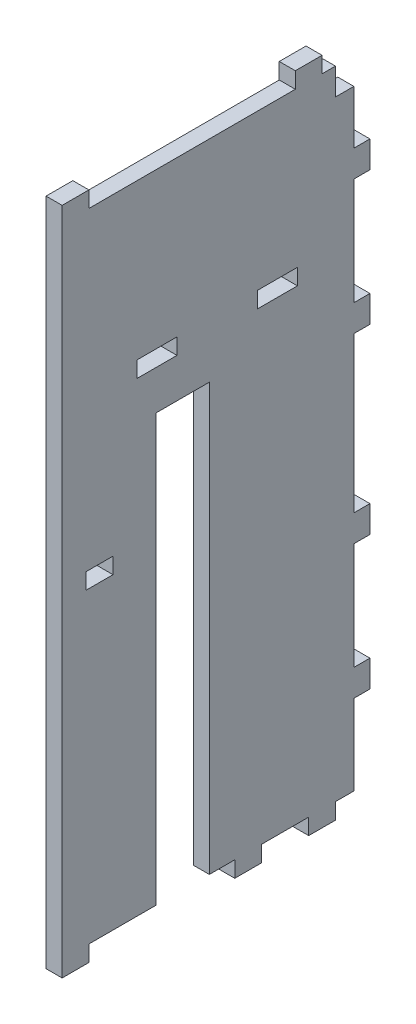
SolidWorks part; units mm, degrees
ref_plane "Plan de face" through (0, 0, 0) normal (0, 0, 1) x (1, 0, 0)
ref_plane "Plan de dessus" through (0, 0, 0) normal (0, 1, 0) x (1, 0, 0)
ref_plane "Plan de droite" through (0, 0, 0) normal (1, 0, 0) x (0, 0, -1)
sketch "Esquisse1" plane through (0, 0, 0) normal (1, 0, 0) x (0, 0, -1)
  line L0 (97.1531, 0) -> (-102.2664, 0) construction
  line L1 (-54.5, 119) -> (54.5, 119)
  line L2 (-54.5, 119) -> (-54.5, -119)
  line L3 (-54.5, -119) -> (54.5, -119)
  line L4 (54.5, 119) -> (54.5, -119)
  line L5 (0, 172.7153) -> (0, -236.1933) construction
  line L7 (-45.5, 2) -> (-35.5, 2)
  line L8 (-45.5, 2) -> (-45.5, -4)
  line L9 (-45.5, -4) -> (-35.5, -4)
  line L10 (-35.5, 2) -> (-35.5, -4)
  line L15 (-26.585, 61) -> (-11.585, 61)
  line L16 (-26.585, 61) -> (-26.585, 55)
  line L17 (-26.585, 55) -> (-11.585, 55)
  line L18 (-11.585, 61) -> (-11.585, 55)
  line L19 (18.415, 61) -> (33.415, 61)
  line L20 (18.415, 61) -> (18.415, 55)
  line L21 (18.415, 55) -> (33.415, 55)
  line L22 (33.415, 61) -> (33.415, 55)
  dimension "D1" = 238
  dimension "D2" = 109
  dimension "D4" = 119
  dimension "D13" = 15
  dimension "D14" = 15
  dimension "D15" = 30
  dimension "D16" = 6
  dimension "D17" = 6
  dimension "D3" = 54.5
  dimension "D5" = 58
  dimension "D6" = 27.915
  dimension "D7" = 9
  dimension "D8" = 117
  dimension "D9" = 6
  dimension "D10" = 10
extrude "Boss.-Extru.1" add sketch "Esquisse1" along normal blind 6
sketch "Esquisse3" plane through (6, 0, 0) normal (1, 0, 0) x (0, 0, -1)
  line L0 (-54.5, -119) -> (54.5, -119) construction
  line L1 (-54.5, -119) -> (-44.5, -119)
  line L2 (-54.5, -119) -> (-54.5, -125)
  line L3 (-54.5, -125) -> (-44.5, -125)
  line L4 (-44.5, -119) -> (-44.5, -125)
  line L5 (245.3741, 0) -> (-166.5298, 0) construction
  line L6 (54.5, -119) -> (54.5, 119) construction
  line L7 (37.62, -119) -> (47.62, -119)
  line L8 (37.62, -119) -> (37.62, -125)
  line L9 (37.62, -125) -> (47.62, -125)
  line L10 (0, 208.6671) -> (0, -232.3841) construction
  line L11 (-54.5, -119) -> (54.5, -119) construction
  line L12 (47.62, -119) -> (47.62, -125)
  line L13 (60.5, 39) -> (60.5, 29)
  line L14 (54.5, 29) -> (60.5, 29)
  line L15 (54.5, 39) -> (54.5, 29)
  line L16 (54.5, 39) -> (60.5, 39)
  line L17 (60.5, 89) -> (60.5, 79)
  line L18 (54.5, 79) -> (60.5, 79)
  line L19 (54.5, 89) -> (54.5, 79)
  line L20 (54.5, 89) -> (60.5, 89)
  line L21 (54.5, 119) -> (-54.5, 119) construction
  line L22 (54.5, -89) -> (60.5, -89)
  line L23 (54.5, -89) -> (54.5, -79)
  line L24 (54.5, -79) -> (60.5, -79)
  line L25 (60.5, -89) -> (60.5, -79)
  line L26 (54.5, -39) -> (60.5, -39)
  line L27 (54.5, -39) -> (54.5, -29)
  line L28 (54.5, -29) -> (60.5, -29)
  line L29 (0, -208.6671) -> (0, 232.3841) construction
  line L30 (10, -119) -> (20, -119)
  line L31 (10, -119) -> (10, -125)
  line L32 (10, -125) -> (20, -125)
  line L33 (20, -119) -> (20, -125)
  line L34 (54.5, -119) -> (54.5, 119) construction
  line L35 (60.5, -39) -> (60.5, -29)
  line L36 (42.62, 119) -> (32.62, 119)
  line L37 (42.62, 119) -> (42.62, 125)
  line L38 (42.62, 125) -> (32.62, 125)
  line L39 (32.62, 119) -> (32.62, 125)
  line L50 (-44.5, 119) -> (-44.5, 125)
  line L51 (-54.5, 125) -> (-44.5, 125)
  line L52 (-54.5, 119) -> (-54.5, 125)
  line L53 (-54.5, 119) -> (-44.5, 119)
  dimension "D2" = 10
  dimension "D3" = 6
  dimension "D4" = 10
  dimension "D5" = 6.88
  dimension "D6" = 6
  dimension "D7" = 6
  dimension "D8" = 10
  dimension "D9" = 6
  dimension "D10" = 10
  dimension "D11" = 6
  dimension "D12" = 10
  dimension "D13" = 17.62
  dimension "D14" = 30
  dimension "D15" = 40
  dimension "D16" = 6
  dimension "D17" = 10
  dimension "D18" = 11.88
extrude "Boss.-Extru.5" add sketch "Esquisse3" against normal blind 6
sketch "Esquisse6" plane through (6, 0, 0) normal (1, 0, 0) x (0, 0, -1)
  line L0 (-44.5, -119) -> (10, -119) construction
  line L1 (-19.5, -119) -> (0.5, -119)
  line L2 (-19.5, -119) -> (-19.5, 40.29)
  line L3 (-19.5, 40.29) -> (0.5, 40.29)
  line L4 (0.5, -119) -> (0.5, 40.29)
  line L5 (54.5, -79) -> (54.5, -39) construction
  line L6 (-44.5, 125) -> (-54.5, 125) construction
  dimension "D1" = 20
  dimension "D2" = 84.71
  dimension "D3" = 54
extrude "Enlèv. mat.-Extru.2" cut sketch "Esquisse6" against normal blind 6
sketch "Esquisse7" plane through (0, 0, 0) normal (-1, 0, 0) x (0, 0, 1)
  line L1 (-54.5, 119) -> (-47.62, 119)
  line L2 (-54.5, 119) -> (-54.5, 109)
  line L3 (-54.5, 109) -> (-47.62, 109)
  line L4 (-47.62, 119) -> (-47.62, 109)
  dimension "D1" = 10
  dimension "D2" = 6.88
extrude "Enlèv. mat.-Extru.3" cut sketch "Esquisse7" against normal blind 6
equation "\"D3@Esquisse1\"=\"D2@Esquisse1\"/2"
equation "\"D4@Esquisse1\"=\"D1@Esquisse1\"/2"
